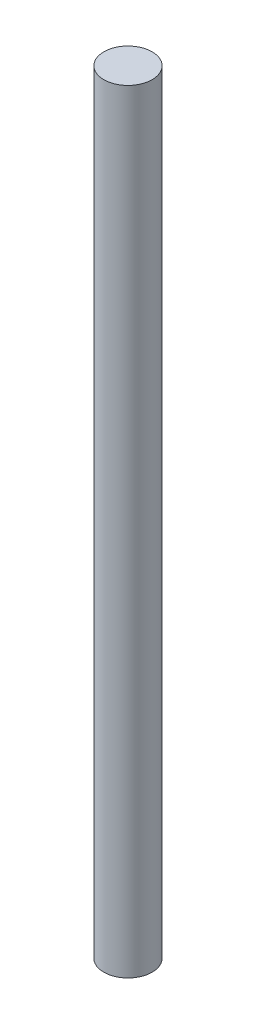
SolidWorks part; units mm, degrees
ref_plane "Front Plane" through (0, 0, 0) normal (0, 0, 1) x (1, 0, 0)
ref_plane "Top Plane" through (0, 0, 0) normal (0, 1, 0) x (1, 0, 0)
ref_plane "Right Plane" through (0, 0, 0) normal (1, 0, 0) x (0, 0, -1)
sketch "Sketch1" plane through (0, 0, 0) normal (0, 1, 0) x (1, 0, 0)
  circle A0 centre (0, 0) radius 3.175
  dimension "D1" = 6.35
extrude "Boss-Extrude1" add sketch "Sketch1" along normal blind 101.6
ref_axis "Axis1" through (0, 0, 0) along (0, 1, 0)
